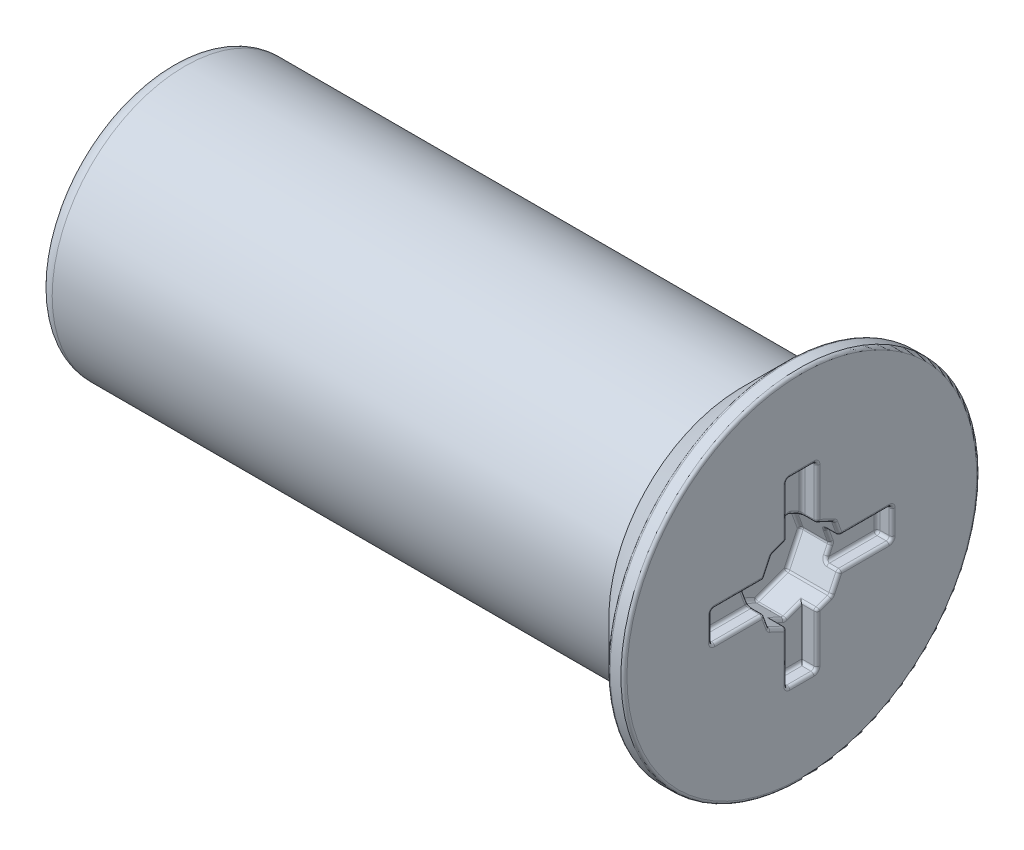
SolidWorks part; units mm, degrees
material "moto_grey"
ref_plane "Front Plane" through (0, 0, 0) normal (0, 0, 1) x (1, 0, 0)
ref_plane "Top Plane" through (0, 0, 0) normal (0, 1, 0) x (1, 0, 0)
ref_plane "Right Plane" through (0, 0, 0) normal (1, 0, 0) x (0, 0, -1)
sketch "Sketch1" plane through (0, 0, 0) normal (1, 0, 0) x (0, 0, -1)
  circle A0 centre (0, 0) radius 11.825
  dimension "D1" = 23.65
extrude "Boss-Extrude1" add sketch "Sketch1" against normal blind 4
chamfer "Chamfer1" distance 3 angle 45 1 edges at (-4, 0, -11.825)
sketch "Sketch2" plane through (-4, 0, 0) normal (-1, 0, 0) x (0, 0, 1)
  circle A2 centre (0, 0) radius 8.825
  circle A3 centre (0, 0) radius 8.825
  dimension "D1" = 0
extrude "Boss-Extrude2" add sketch "Sketch2" along normal blind 38
fillet "Fillet2" radius 1 1 edges at (-42, 0, 8.825)
sketch "Sketch3" plane through (0, 0, 0) normal (1, 0, 0) x (0, 0, -1)
  line L1 (-6, -1) -> (6, -1)
  line L2 (-6, -1) -> (-6, 1)
  line L3 (-6, 1) -> (6, 1)
  line L4 (6, -1) -> (6, 1)
  line L5 (-6, -1) -> (6, 1) construction
  line L6 (-6, 1) -> (6, -1) construction
  line L7 (-1, -6) -> (1, -6)
  line L8 (-1, -6) -> (-1, 6)
  line L9 (-1, 6) -> (1, 6)
  line L10 (1, -6) -> (1, 6)
  line L11 (-1, -6) -> (1, 6) construction
  line L12 (-1, 6) -> (1, -6) construction
  line L13 (2.1548, 1.967) -> (0.1328, 2.9146)
  line L14 (0.1328, 2.9146) -> (-1.967, 2.1548)
  line L15 (-1.967, 2.1548) -> (-2.9146, 0.1328)
  line L16 (-2.9146, 0.1328) -> (-2.1548, -1.967)
  line L17 (-2.1548, -1.967) -> (-0.1328, -2.9146)
  line L18 (-0.1328, -2.9146) -> (1.967, -2.1548)
  line L19 (1.967, -2.1548) -> (2.9146, -0.1328)
  line L20 (2.9146, -0.1328) -> (2.1548, 1.967)
  circle A0 centre (0, 0) radius 2.6955 construction
  point P0 (0, 0)
  point P6 (0, 0)
  dimension "D1" = 2
  dimension "D2" = 12
  dimension "D3" = 2
  dimension "D4" = 12
extrude "Cut-Extrude1" cut sketch "Sketch3" against normal blind 1 contours L20 L19 L1 L4 L3 | L19 L20 L3 L10 L1 | L3 L20 L13 L10 | L13 L14 L8 L3 L10 | L1 L10 L3 L8 | L17 L18 L10 L1 L8 | L18 L17 L8 L7 L10 | L18 L19 L1 L10 | L16 L17 L8 L1 | L15 L16 L1 L8 L3 | L14 L15 L3 L8 | L16 L15 L3 L2 L1 | L14 L13 L10 L9 L8 region at (0, -0.0029, 4.3531) region at (0, 0.0056, 1.8593) region at (0, -1.5962, 1.6132) region at (0, 0, 0) region at (0, -1.8593, 0.0056) region at (0, 1.6132, 1.5962) region at (0, -0.0056, -1.8593) region at (0, -1.6132, -1.5962) region at (0, -4.3531, -0.0029) region at (0, 1.8593, -0.0056) region at (0, 0.0029, -4.3531) region at (0, 1.5962, -1.6132) region at (0, 4.3531, 0.0029)
extrude "Cut-Extrude4" cut sketch "Sketch3<7>" against normal blind 3 contours L3 L20 L13 L10 | L13 L14 L8 L3 L10 | L14 L15 L3 L8 | L15 L16 L1 L8 L3 | L16 L17 L8 L1 | L17 L18 L10 L1 L8 | L1 L10 L3 L8 | L18 L19 L1 L10 | L19 L20 L3 L10 L1 region at (0, 0.0056, 1.8593) region at (0, -1.5962, 1.6132) region at (0, 0, 0) region at (0, -1.8593, 0.0056) region at (0, 1.6132, 1.5962) region at (0, -0.0056, -1.8593) region at (0, -1.6132, -1.5962) region at (0, 1.8593, -0.0056) region at (0, 1.5962, -1.6132)
sketch "Sketch3<7>" plane through (0, 0, 0) normal (1, 0, 0) x (0, 0, -1) same geometry as "Sketch3"
fillet "Fillet3" radius 0.2 70 edges at (0, 1, 4.2541) (0, -1, 4.2524) (0, -4.2541, 1) (0, -4.2524, -1) (0, -1, -4.2541) (0, 1, -4.2524) (0, 4.2541, -1) (0, 4.2524, 1) (-0.5, 1, 6) (-0.5, -1, 6) (0, 0, 6) (-0.5, -1, 2.5047) (0, -1.4835, 2.3298) (-1.5, -1.967, 2.1548) (-1, -2.7114, 0.5664) (-0.5, -2.5082, 1) (0, -2.2376, 1.5774) (-0.5, -2.5047, -1) (-1, -2.7097, -0.4336) (-2, -2.9146, 0.1328) (0, -2.3298, -1.4835) (-1.5, -2.1548, -1.967) (-0.5, -1, -2.5082) (0, -1.5774, -2.2376) (-0.5, 1, -2.5047) (-2, -0.1328, -2.9146) (0, 1.4835, -2.3298) (-1.5, 1.967, -2.1548) (-0.5, 2.5082, -1) (0, 2.2376, -1.5774) (-0.5, 2.5047, 1) (-2, 2.9146, -0.1328) (0, 2.3298, 1.4835) (-1.5, 2.1548, 1.967) (-2, 0.1328, 2.9146) (-0.5, 1, 2.5082) (0, 1.5774, 2.2376) (-0.5, -6, 1) (-1, -6, 0) (-0.5, -6, -1) (0, -6, 0) (-0.5, -1, -6) (-0.5, 1, -6) (0, 0, -6) (-0.5, 6, -1) (-0.5, 6, 1) (0, 6, 0) (-1, -1, 4.2524) (-1, 0, 6) (-1, 1, 4.2541) (-1, 0.5664, 2.7114) (-1, -0.4336, 2.7097) (-1, 4.2524, 1) (-1, 6, 0) (-1, 4.2541, -1) (-1, 2.7114, -0.5664) (-1, 2.7097, 0.4336) (-1, 1, -4.2524) (-1, 0, -6) (-1, -1, -4.2541) (-1, -0.5664, -2.7114) (-1, 0.4336, -2.7097) (-3, 2.4408, -1.1438) (-3, 0.9171, -2.5347) (-3, -1.1438, -2.4408) (-3, -2.5347, -0.9171) (-3, -2.4408, 1.1438) (-3, -0.9171, 2.5347) (-3, 1.1438, 2.4408) (-3, 2.5347, 0.9171)
fillet "Fillet4" radius 0.2 2 edges at (-1, 0, -11.825) (0, 0, -11.825)
